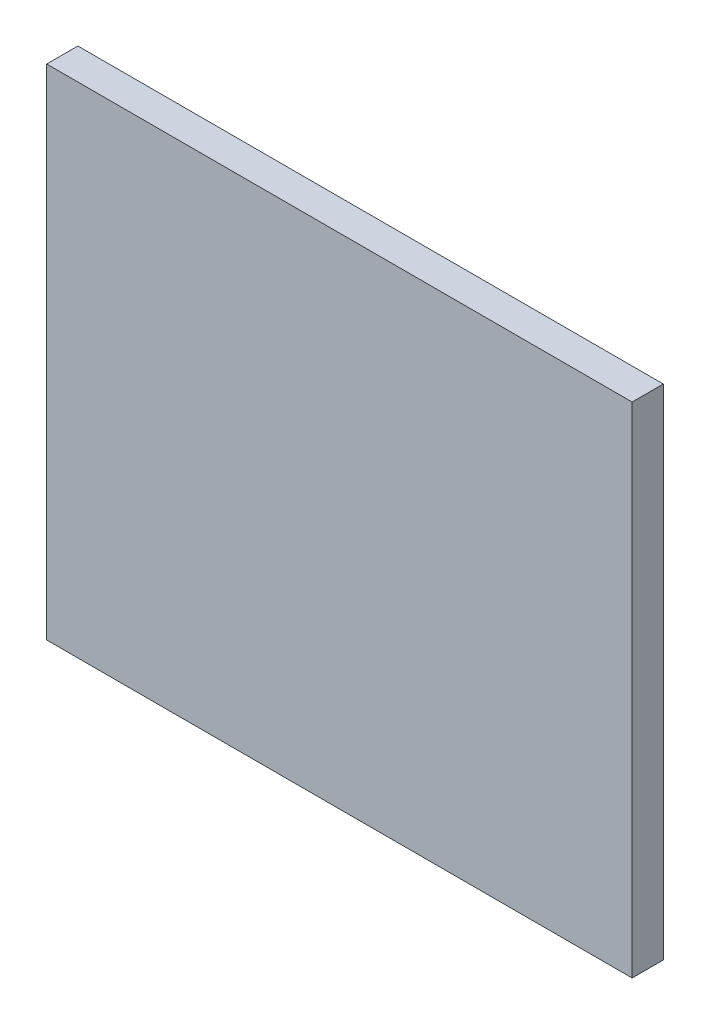
SolidWorks part; units mm, degrees
ref_plane "Front Plane" through (0, 0, 0) normal (0, 0, 1) x (1, 0, 0)
ref_plane "Top Plane" through (0, 0, 0) normal (0, 1, 0) x (1, 0, 0)
ref_plane "Right Plane" through (0, 0, 0) normal (1, 0, 0) x (0, 0, -1)
sketch "Sketch1" plane through (0, 0, 0) normal (0, 0, 1) x (1, 0, 0)
  line L1 (42.25, -36) -> (-42.25, -36)
  line L2 (42.25, -36) -> (42.25, 36)
  line L3 (42.25, 36) -> (-42.25, 36)
  line L4 (-42.25, -36) -> (-42.25, 36)
  line L5 (42.25, -36) -> (-42.25, 36) construction
  line L6 (42.25, 36) -> (-42.25, -36) construction
  point P0 (0, 0)
  dimension "D1" = 72
  dimension "D2" = 84.5
extrude "Boss-Extrude1" add sketch "Sketch1" along normal blind 4.5
